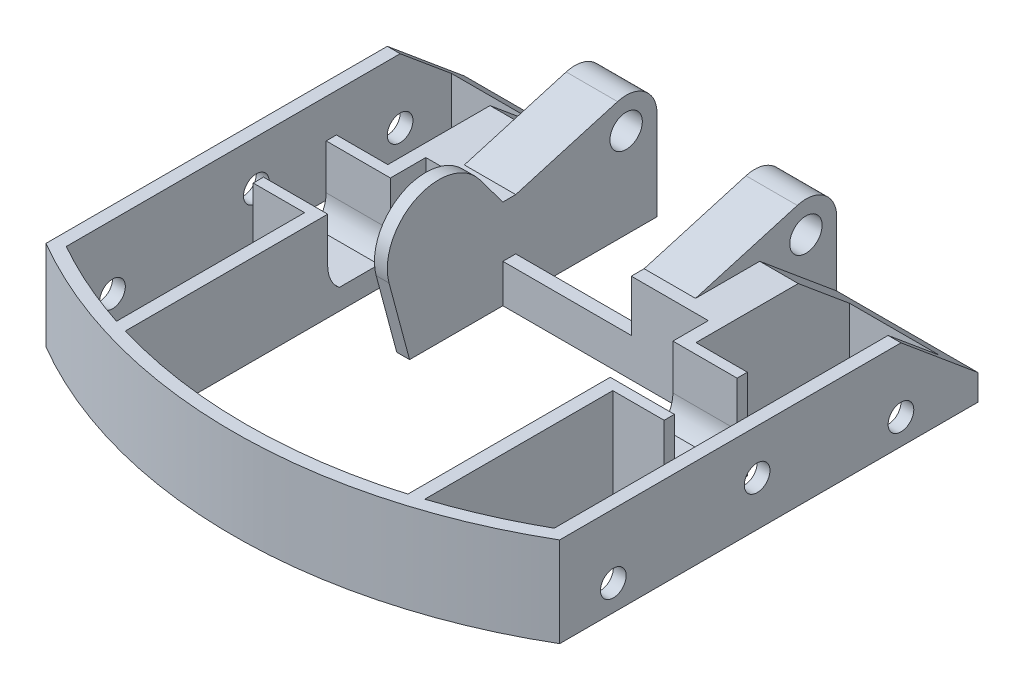
SolidWorks part; units mm, degrees
material "ABS"
ref_plane "Front Plane" through (0, 0, 0) normal (0, 0, 1) x (1, 0, 0)
ref_plane "Top Plane" through (0, 0, 0) normal (0, 1, 0) x (1, 0, 0)
ref_plane "Right Plane" through (0, 0, 0) normal (1, 0, 0) x (0, 0, -1)
sketch "Sketch1" plane through (0, 0, 0) normal (0, 1, 0) x (1, 0, 0)
  line L0 (-15.875, 34.925) -> (-15.875, 0)
  line L1 (-15.875, 0) -> (15.875, 0)
  line L2 (15.875, 0) -> (15.875, 34.925)
  line L3 (-15.875, 34.925) -> (-63.5, 34.925)
  line L4 (-63.5, 34.925) -> (-63.5, -68.5113)
  line L5 (-34.925, -77.4683) -> (-34.925, -3.175)
  line L6 (-34.925, -3.175) -> (34.925, -3.175)
  line L7 (34.925, -3.175) -> (34.925, -77.4683)
  line L9 (-38.1, 0) -> (-38.1, -76.4773)
  line L10 (63.5, -68.5113) -> (63.5, 34.925)
  line L11 (15.875, 34.925) -> (63.5, 34.925)
  line L12 (-38.1, 28.575) -> (-60.325, 28.575)
  line L13 (-60.325, 28.575) -> (-60.325, -66.675)
  line L15 (-38.1, 28.575) -> (-38.1, 0)
  line L16 (0, 0) -> (0, 35.4142) construction
  line L17 (38.1, 0) -> (38.1, -76.4773)
  line L18 (60.325, 28.575) -> (60.325, -66.675)
  line L19 (38.1, 28.575) -> (60.325, 28.575)
  line L20 (38.1, 28.575) -> (38.1, 0)
  arc A0 (-63.5, -68.5113) -> (63.5, -68.5113) centre (0, 40.005) ccw
  arc A1 (-60.325, -66.675) -> (60.325, -66.675) centre (0, 40.005) ccw
  point P8 (0, -82.55)
  point P10 (0, -3.175)
  point P29 (0, -3.175)
  dimension "D8" = 3.175
  dimension "D5" = 3.175
  dimension "D1" = 31.75
  dimension "D2" = 34.925
  dimension "D3" = 25.4
  dimension "D4" = 22.225
  dimension "D6" = 95.25
  dimension "D7" = 15.875
  dimension "D9" = 6.35
  dimension "D10" = 3.175
  dimension "D11" = 3.175
extrude "Boss-Extrude1" add sketch "Sketch1" along normal blind 22.225 contours L11 L2 L1 L0 L3 L4 L10 L20 L19 L18 L12 L15 L13 region at (-17.6267, 0, -17.4625)
sketch "Sketch3" plane through (-63.5, 0, 0) normal (-1, 0, 0) x (0, 0, 1)
  line L0 (-34.925, 6.35) -> (-15.875, 22.225)
  line L1 (-34.925, 22.225) -> (-34.925, 0) construction
  line L2 (-34.925, 22.225) -> (68.5113, 22.225) construction
  dimension "D1" = 6.35
  dimension "D2" = 19.05
extrude "Cut-Extrude3" cut sketch "Sketch3" against normal through all and the other way through all
sketch "Sketch4" plane through (0, 0, 0) normal (1, 0, 0) x (0, 0, -1)
  line L0 (-68.5113, 0) -> (34.925, 0) construction
  line L1 (34.925, 6.35) -> (34.925, 0) construction
  circle A0 centre (27.305, 22.225) radius 28.575
  circle A1 centre (27.305, 22.225) radius 25.4
  circle A2 centre (27.305, 22.225) radius 6.985
  point P3 (0, 0)
  dimension "D1" = 57.15
  dimension "D2" = 50.8
  dimension "D3" = 22.225
  dimension "D5" = 13.97
  dimension "D4" = 7.62
sketch "Sketch7" plane through (-15.875, 0, 0) normal (1, 0, 0) x (0, 0, -1)
  line L0 (34.925, 0) -> (34.925, 22.225)
  line L1 (25.1785, 29.5423) -> (0, 22.225)
  line L2 (-68.5113, 22.225) -> (15.875, 22.225) construction
  line L3 (34.925, 0) -> (0, 0)
  line L4 (0, 0) -> (0, 22.225)
  arc A0 (34.925, 22.225) -> (25.1785, 29.5423) centre (27.305, 22.225) ccw
extrude "Boss-Extrude3" add sketch "Sketch7" against normal blind 12.7
mirror "Mirror1" about plane through (0, 0, 0) normal (1, 0, 0) of "Boss-Extrude3"
sketch "Sketch10" plane through (0, 22.225, 0) normal (0, 1, 0) x (1, 0, 0)
  line L1 (-15.875, 0) -> (15.875, 0)
  line L2 (-15.875, 0) -> (-15.875, -3.175)
  line L3 (-15.875, -3.175) -> (15.875, -3.175)
  line L4 (15.875, 0) -> (15.875, -3.175)
  line L5 (-15.875, 0) -> (15.875, 0) construction
  line L6 (-34.925, -3.175) -> (34.925, -3.175) construction
  point P4 (0, 0)
  point P5 (-12.7, 0)
  point P8 (12.7, 0)
  point P9 (0, 0)
  point P12 (15.875, 0)
  point P18 (-15.068, 0)
extrude "Cut-Extrude5" cut sketch "Sketch10" against normal blind 12.7
ref_axis "Axis1" through (-111.7038, 22.225, -27.305) along (1, 0, 0)
ref_plane "Plane2" through (0, 26.5451, -22.1209) normal (0, 0.7682, -0.6402) x (1, 0, 0)
sketch "Sketch8" plane through (0, 26.5451, -22.1209) normal (0, 0.7682, -0.6402) x (1, 0, 0)
  line L1 (-111.7038, 6.7482) -> (116.069, 6.7482) construction
  line L2 (28.575, 6.7482) -> (-28.575, 6.7482)
  line L3 (28.575, 6.7482) -> (28.575, 10.7482)
  line L4 (28.575, 10.7482) -> (-26.425, 10.7482)
  line L7 (-26.425, 9.7482) -> (-26.425, 10.7482)
  line L8 (28.575, 0.4302) -> (28.575, 12.602) construction
  line L12 (-26.425, 9.7482) -> (-28.575, 9.7482)
  line L13 (-28.575, 6.7482) -> (-28.575, 9.7482)
  line L14 (-28.575, 12.602) -> (-28.575, 0.4302) construction
  dimension "D1" = 3
  dimension "D2" = 4
  dimension "D3" = 55
revolve "Cut-Revolve1" cut sketch "Sketch8" angle 360 about L2
sketch "Sketch9" plane through (-63.5, 0, 0) normal (-1, 0, 0) x (0, 0, 1)
  line L0 (-15.875, 6.35) -> (55.245, 6.35) construction
  line L1 (-28.575, 11.6417) -> (-28.575, 0) construction
  line L2 (66.675, 22.225) -> (66.675, 0) construction
  line L3 (-34.925, 0) -> (68.5113, 0) construction
  line L4 (19.685, 22.225) -> (19.685, 0) construction
  line L5 (-15.875, 22.225) -> (68.5113, 22.225) construction
  circle A0 centre (-15.875, 6.35) radius 11.1125 construction
  circle A1 centre (55.245, 6.35) radius 11.1125 construction
  circle A2 centre (-15.875, 6.35) radius 3.175
  circle A3 centre (55.245, 6.35) radius 3.175
  circle A4 centre (19.685, 11.1125) radius 3.175
  point P7 (-28.575, 5.8208)
  point P15 (19.685, 11.1125)
  point P20 (19.685, 6.35)
  dimension "D1" = 22.225
  dimension "D5" = 6.35
  dimension "D6" = 6.35
  dimension "D2" = 12.7
  dimension "D3" = 11.43
  dimension "D4" = 6.35
extrude "Cut-Extrude4" cut sketch "Sketch9" against normal up to next
mirror "Mirror10" about plane through (0, 0, 0) normal (1, 0, 0) of "Cut-Extrude4"
ref_plane "Plane3" through (-15.875, 0, 0) normal (1, 0, 0) x (0, 0, -1)
sketch "Sketch16" plane through (-15.875, 0, 0) normal (1, 0, 0) x (0, 0, -1)
  line L0 (-85.725, 22.225) -> (42.4531, 51.7851) construction
  line L1 (-68.5113, 22.225) -> (15.875, 22.225) construction
  line L3 (-8.89, 29.845) -> (-3.175, 22.225)
  line L4 (-31.3173, 18.938) -> (-26.2428, 0)
  line L5 (-68.5113, 0) -> (34.925, 0) construction
  line L6 (-26.2428, 0) -> (-3.175, 0)
  line L9 (-3.175, 0) -> (0, 0)
  line L11 (-3.175, 22.225) -> (0, 22.225)
  line L12 (0, 0) -> (0, 22.225)
  arc A0 (-8.89, 29.845) -> (-31.3173, 18.938) centre (-19.05, 22.225) ccw
  circle A2 centre (27.305, 22.225) radius 25.4 construction
  point P1 (-3.175, 21.7881)
  point P14 (0, 0)
  point P18 (0, 0)
  point P23 (0, 0)
  point P26 (0, 0)
  dimension "D1" = 25.4
  dimension "D2" = 15.875
  dimension "D3" = 75
extrude "Boss-Extrude6" add sketch "Sketch16" against normal blind 3.175
sketch "Sketch17" plane through (-38.1, 0, 0) normal (-1, 0, 0) x (0, 0, 1)
  line L0 (24.5904, 5.1125) -> (14.7796, 5.1125)
  line L1 (-15.875, 22.225) -> (68.5113, 22.225) construction
  line L3 (27.435, 11.1125) -> (27.435, 22.225)
  line L4 (27.435, 22.225) -> (11.935, 22.225)
  line L5 (11.935, 11.1125) -> (11.935, 22.225)
  arc A0 (24.5904, 5.1125) -> (27.435, 11.1125) centre (19.685, 11.1125) ccw
  arc A1 (11.935, 11.1125) -> (14.7796, 5.1125) centre (19.685, 11.1125) ccw
  point P12 (0, 0)
  point P13 (0, 0)
extrude "Cut-Extrude8" cut sketch "Sketch17" against normal up to next
mirror "Mirror11" about plane through (0, 0, 0) normal (1, 0, 0) of "Cut-Extrude8"
sketch "Sketch18" plane through (38.1, 0, 0) normal (1, 0, 0) x (0, 0, -1)
  line L0 (-11.935, 22.225) -> (-11.935, 11.1125) construction
  line L1 (-27.435, 11.1125) -> (-27.435, 22.225) construction
  line L2 (-14.7796, 5.1125) -> (-24.5904, 5.1125) construction
  line L3 (-11.935, 22.225) -> (-11.935, 11.1125)
  line L4 (-14.7796, 5.1125) -> (-24.5904, 5.1125)
  line L5 (-27.435, 11.1125) -> (-27.435, 22.225)
  line L6 (-27.435, 22.225) -> (-29.975, 22.225)
  line L7 (-68.5113, 22.225) -> (15.875, 22.225) construction
  line L8 (-29.975, 22.225) -> (-29.975, 0)
  line L9 (-68.5113, 0) -> (34.925, 0) construction
  line L10 (-29.975, 0) -> (-9.395, 0)
  line L11 (-9.395, 0) -> (-9.395, 22.225)
  line L12 (-9.395, 22.225) -> (-11.935, 22.225)
  arc A0 (-27.435, 11.1125) -> (-24.5904, 5.1125) centre (-19.685, 11.1125) ccw construction
  arc A1 (-14.7796, 5.1125) -> (-11.935, 11.1125) centre (-19.685, 11.1125) ccw construction
  arc A2 (-14.7796, 5.1125) -> (-11.935, 11.1125) centre (-19.685, 11.1125) ccw
  arc A3 (-27.435, 11.1125) -> (-24.5904, 5.1125) centre (-19.685, 11.1125) ccw
  point P2 (-11.935, 16.6687)
  dimension "D1" = 2.54
extrude "Boss-Extrude7" add sketch "Sketch18" along normal blind 12.7
mirror "Mirror12" about plane through (0, 0, 0) normal (1, 0, 0) of "Boss-Extrude7"
